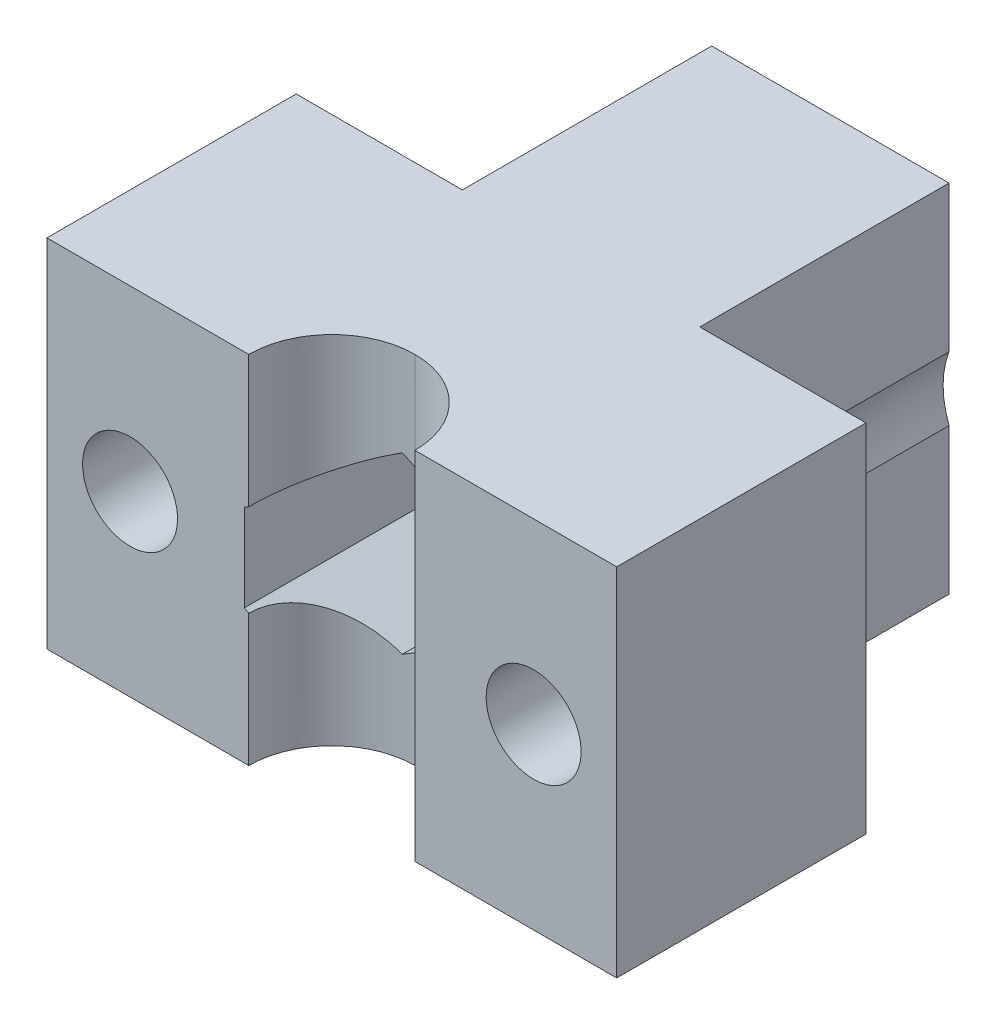
SolidWorks part; units mm, degrees
ref_plane "Спереди" through (0, 0, 0) normal (0, 0, 1) x (1, 0, 0)
ref_plane "Сверху" through (0, 0, 0) normal (0, 1, 0) x (1, 0, 0)
ref_plane "Справа" through (0, 0, 0) normal (1, 0, 0) x (0, 0, -1)
sketch "Эскиз1" plane through (0, 0, 0) normal (0, 1, 0) x (1, 0, 0)
  line L1 (-24, -10) -> (24, -10)
  line L2 (-24, -10) -> (-24, 10)
  line L3 (-24, 10) -> (24, 10)
  line L4 (24, -10) -> (24, 10)
  line L5 (-24, -10) -> (24, 10) construction
  line L6 (-24, 10) -> (24, -10) construction
  point P0 (0, 0)
  dimension "D1" = 48
  dimension "D2" = 20
extrude "Бобышка-Вытянуть1" add sketch "Эскиз1" along normal blind 30
sketch "Эскиз2" plane through (0, 0, 10) normal (0, 0, 1) x (1, 0, 0)
  line L0 (-7, 30) -> (-7, 0)
  line L1 (-24, 30) -> (24, 30) construction
  line L2 (-24, 0) -> (24, 0) construction
  line L3 (-7, 0) -> (7, 0)
  line L4 (7, 0) -> (7, 30)
  line L5 (7, 30) -> (-7, 30)
  dimension "D1" = 17
  dimension "D2" = 14
extrude "Вырез-Вытянуть1" cut sketch "Эскиз2" against normal blind 7
sketch "Эскиз7" plane through (24, 0, 0) normal (1, 0, 0) x (0, 0, -1)
  line L1 (32, 30) -> (32, 0)
  line L2 (32, 0) -> (10, 0)
  line L3 (-10, 0) -> (10, 0)
  line L4 (10, 0) -> (10.066, 0.2736)
  line L5 (10, 30) -> (32, 30)
  line L8 (10, 0) -> (10, 30)
  dimension "D3" = 22
extrude "Бобышка-Вытянуть2" add sketch "Эскиз7" against normal blind 48
sketch "Эскиз8" plane through (24, 0, 0) normal (1, 0, 0) x (0, 0, -1)
  line L0 (11, 0) -> (11, 30)
  line L1 (-10, 30) -> (32, 30) construction
  line L2 (11, 30) -> (32, 30)
  line L3 (11, 0) -> (32, 0)
  line L4 (32, 0) -> (32, 30)
  line L5 (-10, 0) -> (32, 0) construction
  point P16 (11, 0)
extrude "Вырез-Вытянуть2" cut sketch "Эскиз8" against normal blind 14
sketch "Эскиз9" plane through (-24, 0, 0) normal (-1, 0, 0) x (0, 0, 1)
  line L0 (-11, 0) -> (-11, 30)
  line L1 (-32, 30) -> (10, 30) construction
  line L2 (-11, 30) -> (-32, 30)
  line L3 (-32, 0) -> (10, 0) construction
  line L4 (-11, 0) -> (-32, 0)
  line L5 (-32, 0) -> (-32, 30)
  point P15 (-11, 0)
extrude "Вырез-Вытянуть3" cut sketch "Эскиз9" against normal blind 14
sketch "Эскиз11" plane through (-10, 0, 0) normal (-1, 0, 0) x (0, 0, 1)
  line L0 (-32, 30) -> (-11, 0) construction
  line L2 (-32, 0) -> (-11, 0) construction
  line L3 (-16.4, 4.9) -> (-16.4, 25.1)
  line L6 (-16.4, 4.9) -> (-26.6, 4.9)
  line L7 (-16.4, 25.1) -> (-26.6, 25.1)
  line L8 (-26.6, 4.9) -> (-26.6, 25.1)
  line L9 (-16.4, 4.9) -> (-26.6, 25.1) construction
  line L10 (-16.4, 25.1) -> (-26.6, 4.9) construction
  point P7 (-21.5, 15)
  point P8 (-21.5, 15)
  dimension "D1" = 20.2
  dimension "D2" = 10.2
extrude "Вырез-Вытянуть4" cut sketch "Эскиз11" against normal through all
sketch "Эскиз13" plane through (0, 0, -11) normal (0, 0, -1) x (-1, 0, 0)
  line L0 (24, 15) -> (10, 15) construction
  line L1 (24, 0) -> (24, 30) construction
  line L2 (10, 0) -> (10, 30) construction
  circle A0 centre (17, 15) radius 4
extrude "Вырез-Вытянуть5" cut sketch "Эскиз13" against normal through all
sketch "Эскиз14" plane through (0, 0, -11) normal (0, 0, -1) x (-1, 0, 0)
  line L0 (-24, 15) -> (-10, 15) construction
  line L1 (-24, 30) -> (-24, 0) construction
  line L2 (-10, 30) -> (-10, 0) construction
  circle A0 centre (-17, 15) radius 4
extrude "Вырез-Вытянуть6" cut sketch "Эскиз14" against normal through all
fillet "Скругление1" radius 7 2 edges at (-7, 15, 3) (7, 15, 3)
sketch "Sketch1" plane through (10, 0, 0) normal (1, 0, 0) x (0, 0, -1)
  line L0 (16.4, 25.1) -> (26.6, 4.9) construction
  line L2 (26.6, 4.9) -> (16.4, 4.9)
  line L3 (26.6, 4.9) -> (26.6, 25.1)
  line L4 (26.6, 25.1) -> (16.4, 25.1)
  line L5 (16.4, 4.9) -> (16.4, 25.1)
  line L6 (26.6, 4.9) -> (16.4, 25.1) construction
  line L7 (26.6, 25.1) -> (16.4, 4.9) construction
  point P4 (21.5, 15)
extrude "Boss-Extrude1" add sketch "Sketch1" against normal blind 4
sketch "Эскиз20" plane through (0, 0, -11) normal (0, 0, -1) x (-1, 0, 0)
  circle A0 centre (-17, 15) radius 7.5
  circle A1 centre (17, 15) radius 7.5
  dimension "D1" = 15
extrude "Вырез-Вытянуть8" cut sketch "Эскиз20" along normal through all
sketch "Sketch3" plane through (0, 0, -32) normal (0, 0, -1) x (-1, 0, 0)
  line L0 (1, 30) -> (1, 0) construction
  line L1 (10, 30) -> (-10, 30) construction
  line L2 (10, 0) -> (-10, 0) construction
  circle A0 centre (1, 15) radius 4
  dimension "D1" = 8
  dimension "D2" = 9
extrude "Cut-Extrude2" cut sketch "Sketch3" against normal through all
sketch "Sketch4" plane through (0, 0, -32) normal (0, 0, -1) x (-1, 0, 0)
  line L1 (1, 22.35) -> (-5.3653, 18.675)
  line L2 (-5.3653, 18.675) -> (-5.3653, 11.325)
  line L3 (-5.3653, 11.325) -> (1, 7.65)
  line L4 (1, 7.65) -> (7.3653, 11.325)
  line L5 (7.3653, 11.325) -> (7.3653, 18.675)
  line L6 (7.3653, 18.675) -> (1, 22.35)
  circle A0 centre (1, 15) radius 7.35 construction
extrude "Cut-Extrude3" cut sketch "Sketch4" against normal blind 20 from offset 25 offset against normal yes
